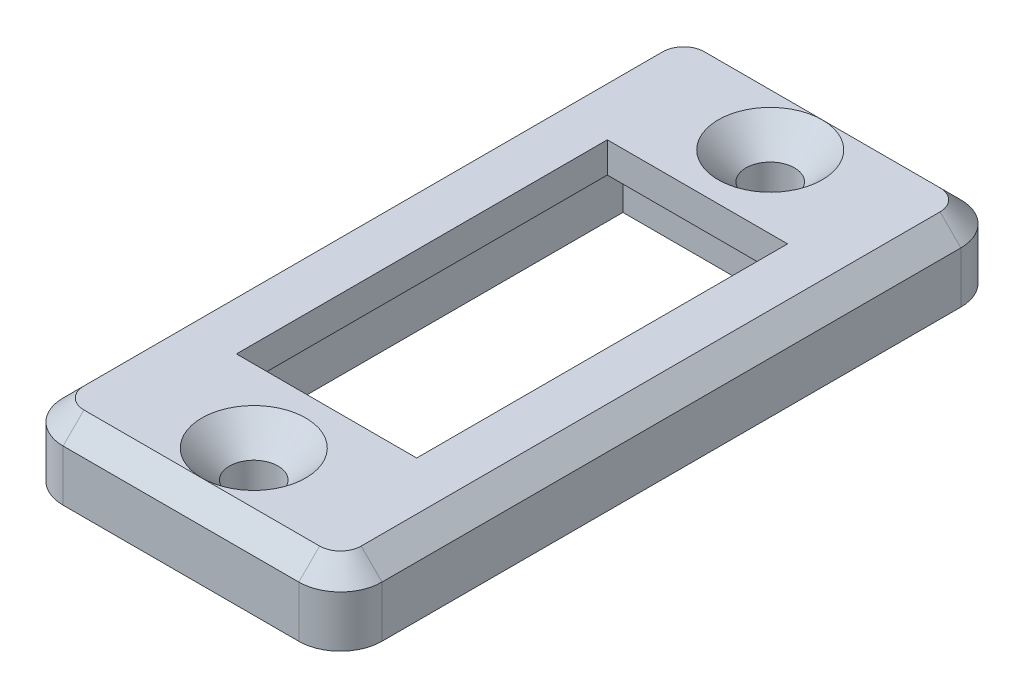
SolidWorks part; units mm, degrees
ref_plane "Спереди" through (0, 0, 0) normal (0, 0, 1) x (1, 0, 0)
ref_plane "Сверху" through (0, 0, 0) normal (0, 1, 0) x (1, 0, 0)
ref_plane "Справа" through (0, 0, 0) normal (1, 0, 0) x (0, 0, -1)
sketch "Эскиз1" plane through (0, 0, 0) normal (0, 1, 0) x (1, 0, 0)
  line L0 (0, 18.625) -> (0, -18.625) construction
  line L1 (6.5, -13.375) -> (-6.5, -13.375)
  line L2 (6.5, -13.375) -> (6.5, 13.375)
  line L3 (6.5, 13.375) -> (-6.5, 13.375)
  line L4 (-6.5, -13.375) -> (-6.5, 13.375)
  line L5 (6.5, -13.375) -> (-6.5, 13.375) construction
  line L6 (6.5, 13.375) -> (-6.5, -13.375) construction
  line L7 (8.5, -23.875) -> (-8.5, -23.875)
  line L8 (11.5, -20.875) -> (11.5, 20.875)
  line L9 (8.5, 23.875) -> (-8.5, 23.875)
  line L10 (-11.5, -20.875) -> (-11.5, 20.875)
  line L11 (11.5, -23.875) -> (-11.5, 23.875) construction
  line L12 (11.5, 23.875) -> (-11.5, -23.875) construction
  line L13 (-2.7569, 13.375) -> (-2.7569, 23.875) construction
  circle A0 centre (0, 18.625) radius 1.75
  circle A1 centre (0, -18.625) radius 1.75
  arc A2 (11.5, -20.875) -> (8.5, -23.875) centre (8.5, -20.875) cw
  arc A3 (11.5, 20.875) -> (8.5, 23.875) centre (8.5, 20.875) ccw
  arc A4 (-11.5, 20.875) -> (-8.5, 23.875) centre (-8.5, 20.875) cw
  arc A5 (-11.5, -20.875) -> (-8.5, -23.875) centre (-8.5, -20.875) ccw
  point P0 (0, 0)
  point P6 (0, 0)
  point P13 (0, 0)
  point P18 (-2.7569, 18.625)
  point P19 (0, 0)
  point P20 (0, -16.2992)
  dimension "D4" = 3.5
  dimension "D6" = 3
  dimension "D1" = 13
  dimension "D2" = 5
  dimension "D3" = 26.75
  dimension "D5" = 10.5
extrude "Бобышка-Вытянуть1" add sketch "Эскиз1" along normal blind 2.2
sketch "Эскиз2" plane through (0, 0, 0) normal (0, -1, 0) x (1, 0, 0)
  line L0 (8.5, -23.875) -> (-8.5, -23.875) construction
  line L1 (-11.5, -20.875) -> (-11.5, 20.875) construction
  line L2 (-8.5, 23.875) -> (8.5, 23.875) construction
  line L3 (11.5, 20.875) -> (11.5, -20.875) construction
  line L4 (8.5, -23.875) -> (-8.5, -23.875)
  line L5 (-11.5, -20.875) -> (-11.5, 20.875)
  line L6 (-8.5, 23.875) -> (8.5, 23.875)
  line L7 (11.5, 20.875) -> (11.5, -20.875)
  line L9 (-6.6, -14.6) -> (6.6, -14.6)
  line L10 (-6.6, -14.6) -> (-6.6, 14.6)
  line L11 (-6.6, 14.6) -> (6.6, 14.6)
  line L12 (6.6, -14.6) -> (6.6, 14.6)
  line L13 (-6.6, -14.6) -> (6.6, 14.6) construction
  line L14 (-6.6, 14.6) -> (6.6, -14.6) construction
  arc A0 (8.5, -23.875) -> (11.5, -20.875) centre (8.5, -20.875) ccw construction
  arc A1 (-11.5, -20.875) -> (-8.5, -23.875) centre (-8.5, -20.875) ccw construction
  circle A2 centre (0, 18.625) radius 1.75 construction
  arc A3 (-8.5, 23.875) -> (-11.5, 20.875) centre (-8.5, 20.875) ccw construction
  arc A4 (11.5, 20.875) -> (8.5, 23.875) centre (8.5, 20.875) ccw construction
  arc A5 (8.5, -23.875) -> (11.5, -20.875) centre (8.5, -20.875) ccw
  arc A6 (-11.5, -20.875) -> (-8.5, -23.875) centre (-8.5, -20.875) ccw
  circle A7 centre (0, 18.625) radius 1.75
  arc A8 (-8.5, 23.875) -> (-11.5, 20.875) centre (-8.5, 20.875) ccw
  arc A9 (11.5, 20.875) -> (8.5, 23.875) centre (8.5, 20.875) ccw
  circle A10 centre (0, -18.625) radius 1.75 construction
  circle A11 centre (0, -18.625) radius 1.75
  point P18 (0, 0)
  dimension "D1" = 29.2
  dimension "D2" = 13.2
extrude "Бобышка-Вытянуть2" add sketch "Эскиз2" along normal blind 3
chamfer "Фаска1" distance 2 angle 45 2 edges at (0, 2.2, -16.875) (0, 2.2, 20.375)
chamfer "Фаска2" distance 1.5 angle 45 8 edges at (-11.5, 2.2, 0) (-10.6213, 2.2, 22.9963) (-10.6213, 2.2, -22.9963) (0, 2.2, 23.875) (0, 2.2, -23.875) (10.6213, 2.2, 22.9963) (10.6213, 2.2, -22.9963) (11.5, 2.2, 0)
